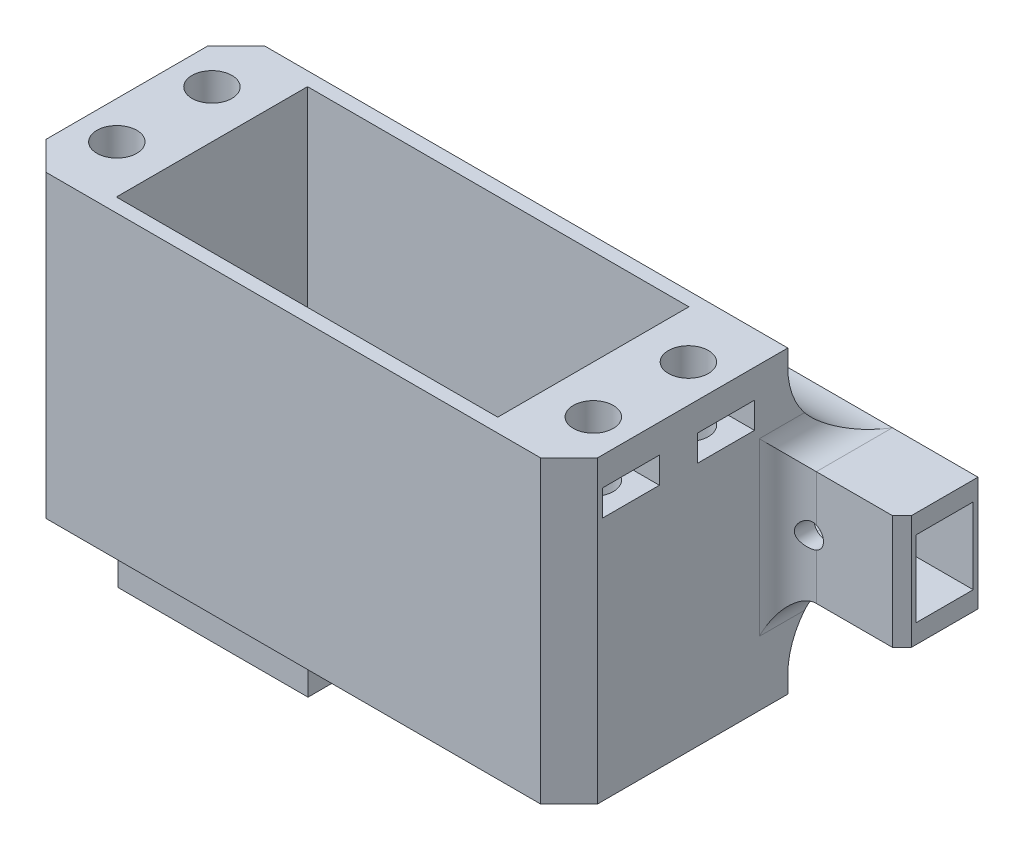
SolidWorks part; units mm, degrees
ref_plane "Front Plane" through (0, 0, 0) normal (0, 0, 1) x (1, 0, 0)
ref_plane "Top Plane" through (0, 0, 0) normal (0, 1, 0) x (1, 0, 0)
ref_plane "Right Plane" through (0, 0, 0) normal (1, 0, 0) x (0, 0, -1)
sketch "Sketch1" plane through (0, 0, 0) normal (0, 1, 0) x (1, 0, 0)
  line L0 (9.9, 0.4273) -> (50, 0.4273)
  line L1 (50, 0.4273) -> (50, -19.6727)
  line L2 (50, -19.6727) -> (9.9, -19.6727)
  line L4 (0.95, -21.1227) -> (58.95, -21.1227)
  line L5 (58.95, -21.1227) -> (58.95, 1.8773)
  line L6 (58.95, 1.8773) -> (0.95, 1.8773)
  line L8 (55, -4.6227) -> (55, -14.6227) construction
  line L9 (0.95, 1.8773) -> (0.95, -21.1227)
  line L10 (9.9, 0.4273) -> (9.9, -19.6727)
  line L11 (29.95, 0.4273) -> (29.95, -19.6727) construction
  circle A0 centre (55, -4.6227) radius 2.1
  circle A1 centre (55, -14.6227) radius 2.1
  circle A2 centre (4.9, -14.6227) radius 2.1
  circle A3 centre (4.9, -4.6227) radius 2.1
  point P13 (55, -9.6227)
  point P14 (50, -9.6227)
  point P20 (0.95, -9.6227)
  point P22 (29.95, 1.8773)
  dimension "D1" = 4.2
  dimension "D2" = 10
  dimension "D3" = 23
  dimension "D4" = 40.1
  dimension "D5" = 5
  dimension "D6" = 20.1
  dimension "D7" = 58
extrude "Boss-Extrude1" add sketch "Sketch1" along normal blind 28.35
sketch "Sketch11" plane through (0, 0, 0) normal (0, -1, 0) x (1, 0, 0)
  line L1 (0.95, 21.1227) -> (58.95, 21.1227)
  line L2 (0.95, 21.1227) -> (0.95, -1.8773)
  line L3 (0.95, -1.8773) -> (58.95, -1.8773)
  line L4 (58.95, 21.1227) -> (58.95, -1.8773)
extrude "Boss-Extrude5" add sketch "Sketch11" along normal blind 3.175
sketch "Sketch14" plane through (0, 0, -1.8773) normal (0, 0, -1) x (-1, 0, 0)
  line L7 (-58.95, 28.35) -> (-58.95, -3.175) construction
  line L8 (-46.95, 6.5875) -> (-70.95, 6.5875)
  line L9 (-46.95, 6.5875) -> (-46.95, 18.5875)
  line L10 (-46.95, 18.5875) -> (-70.95, 18.5875)
  line L11 (-70.95, 6.5875) -> (-70.95, 18.5875)
  line L12 (-46.95, 6.5875) -> (-70.95, 18.5875) construction
  line L13 (-46.95, 18.5875) -> (-70.95, 6.5875) construction
  point P0 (-58.95, 12.5875)
  point P5 (-58.95, 12.5875)
  dimension "D1" = 24
  dimension "D2" = 12
  dimension "D3" = 0
extrude "Boss-Extrude7" add sketch "Sketch14" along normal blind 9
ref_plane "Plane1" through (0, 0, -6.3773) normal (0, 0, 1) x (1, 0, 0)
sketch "Sketch16" plane through (0, 0, -6.3773) normal (0, 0, 1) x (1, 0, 0)
  line L0 (70.95, 18.5875) -> (70.95, 6.5875) construction
  line L1 (57.45, 8.5875) -> (70.95, 8.5875)
  line L3 (57.45, 16.5875) -> (70.95, 16.5875)
  line L4 (70.95, 8.5875) -> (70.95, 16.5875)
  line L5 (46.95, 6.5875) -> (46.95, 18.5875) construction
  arc A0 (57.45, 16.5875) -> (57.45, 8.5875) centre (57.45, 12.5875) ccw
  point P9 (46.95, 12.5875)
  dimension "D2" = 4
  dimension "D1" = 13.5
extrude "Cut-Extrude1" cut sketch "Sketch16" against normal mid plane 6
sketch "Sketch18" plane through (0, 0, -10.8773) normal (0, 0, -1) x (-1, 0, 0)
  arc A0 (-60.2, 12.5875) -> (-62.7, 12.5875) centre (-61.45, 12.5875) ccw construction
  arc A1 (-62.7, 12.5875) -> (-60.2, 12.5875) centre (-61.45, 12.5875) ccw construction
  arc A2 (-56.2, 12.5875) -> (-58.7, 12.5875) centre (-57.45, 12.5875) ccw construction
  arc A3 (-58.7, 12.5875) -> (-56.2, 12.5875) centre (-57.45, 12.5875) ccw construction
  arc A4 (-60.2, 12.5875) -> (-62.7, 12.5875) centre (-61.45, 12.5875) ccw
  arc A5 (-62.7, 12.5875) -> (-60.2, 12.5875) centre (-61.45, 12.5875) ccw
  arc A6 (-56.2, 12.5875) -> (-58.7, 12.5875) centre (-57.45, 12.5875) ccw
  arc A7 (-58.7, 12.5875) -> (-56.2, 12.5875) centre (-57.45, 12.5875) ccw
extrude "Cut-Extrude2" cut sketch "Sketch18" against normal up to surface (9 mm away) up to face at (64.95, 12.5875, -1.8773)
fillet "Fillet1" radius 8 3 edges at (52.95, 6.5875, -1.8773) (46.95, 12.5875, -1.8773) (52.95, 18.5875, -1.8773)
chamfer "Chamfer2" distance 3 angle 45 3 edges at (0.95, 12.5875, -1.8773) (0.95, 12.5875, 21.1227) (58.95, 12.5875, 21.1227)
fillet "Fillet2" radius 3 2 edges at (58.95, 6.5875, -5.8773) (58.95, 18.5875, -5.8773)
fillet "Fillet3" radius 3 1 edges at (58.95, 12.5875, -1.8773)
chamfer "Chamfer3" distance 1 angle 45 5 edges at (70.95, 12.5875, -1.8773) (70.95, 12.5875, -10.8773) (58.95, 6.5875, -10.8773) (46.95, 12.5875, -10.8773) (58.95, 18.5875, -10.8773)
ref_plane "Plane2" through (0, 25.35, 0) normal (0, 1, 0) x (1, 0, 0)
sketch "Sketch19" plane through (0, 25.35, 0) normal (0, 1, 0) x (1, 0, 0)
  line L0 (0.95, -1.1227) -> (0.95, -18.1227) construction
  line L1 (0.95, -1.6227) -> (8.95, -1.6227)
  line L2 (0.95, -1.6227) -> (0.95, -7.6227)
  line L3 (0.95, -7.6227) -> (8.95, -7.6227)
  line L4 (8.95, -1.6227) -> (8.95, -7.6227)
  line L5 (-0.5892, -9.6227) -> (60.8708, -9.6227) construction
  line L6 (29.95, -22.0073) -> (29.95, 3.0189) construction
  line L7 (9.9, 0.4273) -> (9.9, -19.6727) construction
  line L8 (50, 0.4273) -> (9.9, 0.4273) construction
  line L9 (8.95, -17.6227) -> (8.95, -11.6227)
  line L10 (0.95, -11.6227) -> (8.95, -11.6227)
  line L11 (0.95, -17.6227) -> (0.95, -11.6227)
  line L12 (0.95, -17.6227) -> (8.95, -17.6227)
  line L37 (60.4892, -9.6227) -> (-0.9708, -9.6227) construction
  line L38 (58.95, -17.6227) -> (50.95, -17.6227)
  line L39 (58.95, -17.6227) -> (58.95, -11.6227)
  line L40 (58.95, -11.6227) -> (50.95, -11.6227)
  line L41 (50.95, -17.6227) -> (50.95, -11.6227)
  line L42 (50.95, -1.6227) -> (50.95, -7.6227)
  line L43 (58.95, -7.6227) -> (50.95, -7.6227)
  line L44 (58.95, -1.6227) -> (58.95, -7.6227)
  line L45 (58.95, -1.6227) -> (50.95, -1.6227)
  circle A0 centre (4.9, -4.6227) radius 2.1 construction
  circle A1 centre (4.9, -4.6227) radius 2.1 construction
  circle A2 centre (4.9, -14.6227) radius 2.1 construction
  circle A3 centre (4.9, -4.6227) radius 2.1 construction
  circle A4 centre (4.9, -14.6227) radius 2.1 construction
  circle A5 centre (4.9, -4.6227) radius 2.1 construction
  circle A6 centre (4.9, -14.6227) radius 2.1 construction
  circle A7 centre (4.9, -4.6227) radius 2.1 construction
  circle A8 centre (4.9, -14.6227) radius 2.1 construction
  circle A9 centre (55, -14.6227) radius 2.1 construction
  circle A10 centre (55, -4.6227) radius 2.1 construction
  circle A11 centre (55, -14.6227) radius 2.1 construction
  circle A12 centre (55, -4.6227) radius 2.1 construction
  circle A13 centre (55, -14.6227) radius 2.1 construction
  circle A14 centre (55, -4.6227) radius 2.1 construction
  circle A15 centre (55, -14.6227) radius 2.1 construction
  circle A16 centre (55, -4.6227) radius 2.1 construction
  point P11 (0.95, -4.6227)
  point P18 (9.9, -9.6227)
  point P21 (29.95, 0.4273)
  point P28 (0.95, -14.6227)
  point P55 (58.95, -14.6227)
  point P56 (58.95, -4.6227)
  dimension "D1" = 6
  dimension "D2" = 8
extrude "Cut-Extrude3" cut sketch "Sketch19" against normal blind 2.75
sketch "Sketch20" plane through (0, 0, 0) normal (0, 1, 0) x (1, 0, 0)
  line L0 (0.95, -1.1227) -> (0.95, -18.1227) construction
  line L1 (0.95, -12.1227) -> (9.9, -12.1227)
  line L2 (0.95, -12.1227) -> (0.95, -7.1227)
  line L3 (0.95, -7.1227) -> (9.9, -7.1227)
  line L4 (9.9, -12.1227) -> (9.9, -7.1227)
  line L5 (9.9, 0.4273) -> (9.9, -19.6727) construction
  point P6 (0.95, -9.6227)
  dimension "D1" = 5
extrude "Cut-Extrude4" cut sketch "Sketch20" along normal blind 3.5
sketch "Sketch21" plane through (0, -3.175, 0) normal (0, -1, 0) x (1, 0, 0)
  line L0 (0.95, 18.1227) -> (0.95, 1.1227) construction
  line L1 (30, -0.3773) -> (10, -0.3773)
  line L2 (30, -0.3773) -> (30, 19.6227)
  line L3 (30, 19.6227) -> (10, 19.6227)
  line L4 (10, -0.3773) -> (10, 19.6227)
  line L5 (30, -0.3773) -> (10, 19.6227) construction
  line L6 (30, 19.6227) -> (10, -0.3773) construction
  point P0 (20, 9.6227)
  point P7 (0.95, 9.6227)
  dimension "D1" = 19.05
  dimension "D2" = 20
  dimension "D3" = 20
extrude "Boss-Extrude8" add sketch "Sketch21" along normal blind 6
sketch "Sketch13" plane through (0, -9.175, 0) normal (0, -1, 0) x (1, 0, 0)
  line L0 (0.95, 18.1227) -> (0.95, 1.1227) construction
  circle A0 centre (20, 9.6227) radius 3
  point P2 (0.95, 9.6227)
  dimension "D2" = 6
  dimension "D1" = 19.05
extrude "Boss-Extrude6" add sketch "Sketch13" along normal blind 5
fillet "Fillet4" radius 1 4 edges at (20, -3.175, 19.6227) (30, -3.175, 9.6227) (20, -3.175, -0.3773) (10, -3.175, 9.6227)
chamfer "Chamfer4" distance 2 angle 45 4 edges at (20, -9.175, 19.6227) (30, -9.175, 9.6227) (20, -9.175, -0.3773) (10, -9.175, 9.6227)
